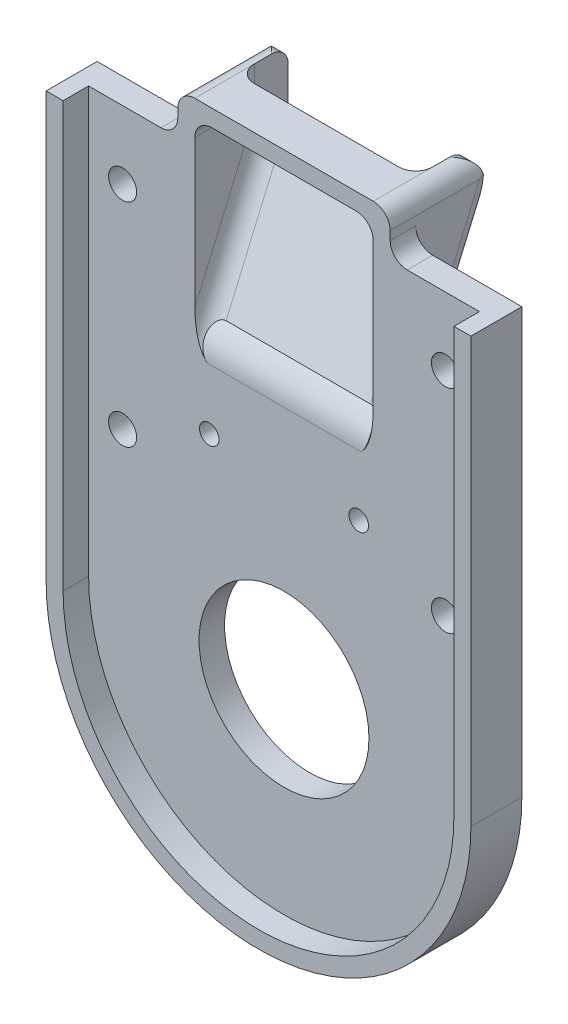
SolidWorks part; units mm, degrees
ref_plane "前视基准面" through (0, 0, 0) normal (0, 0, 1) x (1, 0, 0)
ref_plane "上视基准面" through (0, 0, 0) normal (0, 1, 0) x (1, 0, 0)
ref_plane "右视基准面" through (0, 0, 0) normal (1, 0, 0) x (0, 0, -1)
sketch "草图1" plane through (0, 0, 0) normal (0, 0, 1) x (1, 0, 0)
  line L0 (-25, 0) -> (25, 0)
  line L1 (-25, 0) -> (-25, 50)
  line L2 (25, 0) -> (25, 50)
  line L3 (-25, 50) -> (25, 50)
  line L4 (-23, 0) -> (-23, 50)
  line L5 (23, 0) -> (23, 50)
  circle A0 centre (0, 0) radius 23
  circle A1 centre (0, 0) radius 25
  circle A2 centre (0, 0) radius 10
  circle A3 centre (-19, 17) radius 1.65
  circle A4 centre (19, 17) radius 1.65
  circle A5 centre (19, 42) radius 1.65
  circle A6 centre (-19, 42) radius 1.65
  dimension "D1" = 46
  dimension "D2" = 50
  dimension "D3" = 20
  dimension "D6" = 3.3
  dimension "D4" = 2
  dimension "D5" = 19
  dimension "D7" = 17
  dimension "D10" = 50
  dimension "D8" = 2
  dimension "D9" = 2
extrude "凸台-拉伸3" add sketch "草图1" along normal blind 3 contours A4 A1 L5 L3 L4 A3 A6 A5 | A1 L2 L3 L5 | A1 L4 L3 L1 | A4 A1 A3 L4 A0 L5 | A2 L0 A0 | A2 L0 A0 | L0 A1 A0 | L4 A1 L0 | L0 A1 L5 region at (-23.8028, 3.6947, 0) region at (-24, -0.559, 0) region at (-24.0299, 28.2321, 0) region at (0, 11.0476, 0) region at (-22.4765, 4.899, 0) region at (0, -11.0476, 0) region at (24.0299, 28.2321, 0) region at (23.8028, 3.6947, 0) region at (0, 35.1599, 0)
sketch "草图3" plane through (0, 0, 3) normal (0, 0, 1) x (1, 0, 0)
  line L0 (-23, 0) -> (-23, 50)
  line L1 (23, 0) -> (23, 50)
  line L3 (-25, 50) -> (-25, 0)
  line L4 (25, 0) -> (25, 50)
  line L5 (25, 50) -> (-25, 50)
  line L6 (-25, 50) -> (-25, 0)
  line L7 (25, 0) -> (25, 50)
  line L8 (25, 50) -> (-25, 50)
  circle A0 centre (0, 0) radius 23
  arc A1 (-25, 0) -> (25, 0) centre (0, 0) ccw
  arc A2 (-25, 0) -> (25, 0) centre (0, 0) ccw
  line M6 (-25, 50) -> (-25, 0)
  arc M7 (-25, 0) -> (25, 0) centre (0, 0) ccw
  line M8 (25, 0) -> (25, 50)
  line M9 (25, 50) -> (-25, 50)
  dimension "D2" = 46
  dimension "D1" = 0
extrude "凸台-拉伸4" add sketch "草图3" along normal blind 3 contours A0 L0 L1 M9 M6 M7 M8 region at (0, -23.9014, 3)
sketch "草图4" plane through (0, 0, 3) normal (0, 0, 1) x (1, 0, 0)
  line L0 (0, 50) -> (0, 0) construction
  line L3 (23, 0) -> (23, 50)
  line L4 (23, 50) -> (-23, 50)
  line L5 (-23, 50) -> (-23, 0)
  line L6 (23, 0) -> (23, 50)
  line L7 (23, 50) -> (-23, 50)
  line L8 (-23, 50) -> (-23, 0)
  circle A0 centre (8.8, 21.62) radius 1.15
  arc A1 (-23, 0) -> (23, 0) centre (0, 0) ccw
  arc A2 (-23, 0) -> (23, 0) centre (0, 0) ccw
  circle A3 centre (-8.8, 21.62) radius 1.15
  dimension "D2" = 2.3
  dimension "D3" = 8.8
  dimension "D4" = 28.38
  dimension "D1" = 0
extrude "切除-拉伸1" cut sketch "草图4" against normal blind 10 contours A3 | A0
sketch "草图5" plane through (0, 0, 0) normal (0, 0, -1) x (-1, 0, 0)
  line L1 (-12.5, 50) -> (12.5, 50)
  line L2 (-12.5, 50) -> (-12.5, 30.4832)
  line L3 (25, 0) -> (25, 50)
  line L4 (25, 50) -> (-25, 50)
  line L5 (-25, 50) -> (-25, 0)
  line L6 (25, 0) -> (25, 50)
  line L7 (25, 50) -> (-25, 50)
  line L8 (-25, 50) -> (-25, 0)
  line L9 (-12.5, 30.4832) -> (12.5, 30.4832)
  line L10 (12.5, 50) -> (12.5, 30.4832)
  line L11 (-10.5, 50) -> (-10.5, 32.4832)
  line L12 (-10.5, 32.4832) -> (10.5, 32.4832)
  line L13 (10.5, 32.4832) -> (10.5, 50)
  line L15 (-12.5, 50) -> (-10.5, 50)
  line L16 (-12.5, 50) -> (-12.5, 55)
  line L17 (-12.5, 55) -> (-10.5, 55)
  line L18 (-10.5, 50) -> (-10.5, 55)
  line L19 (10.5, 50) -> (12.5, 50)
  line L20 (10.5, 50) -> (10.5, 55)
  line L21 (10.5, 55) -> (12.5, 55)
  line L22 (12.5, 50) -> (12.5, 55)
  arc A1 (-25, 0) -> (25, 0) centre (0, 0) ccw
  arc A2 (-25, 0) -> (25, 0) centre (0, 0) ccw
  line M11 (25, 50) -> (-25, 50)
  dimension "D2" = 25
  dimension "D3" = 37.5
  dimension "D4" = 2
  dimension "D5" = 2
  dimension "D6" = 2
  dimension "D7" = 5
  dimension "D8" = 5
  dimension "D9" = 19.5168
  dimension "D1" = 0
extrude "凸台-拉伸6" add sketch "草图5" along normal blind 8 contours L13 L12 L11 L7 L2 L9 L10 M11 | L7 L18 L17 L16 | L22 L21 L20 M11 region at (11.5, 52.5, 0) region at (11.5, 49.6828, 0) region at (-11.5, 52.5, 0)
sketch "草图6" plane through (0, 0, 0) normal (0, 0, -1) x (-1, 0, 0)
  line L4 (-10.5, 32.4832) -> (10.5, 32.4832)
  line L5 (10.5, 32.4832) -> (10.5, 50)
  line L7 (10.5, 32.4832) -> (10.5, 50)
  line L8 (-10.5, 32.4832) -> (10.5, 32.4832)
  line L13 (10.5, 50) -> (-10.5, 50)
  line L15 (10.5, 50) -> (-10.5, 50)
  line L16 (-10.5, 50) -> (-10.5, 32.4832)
  line L17 (-10.5, 50) -> (-10.5, 32.4832)
  dimension "D1" = 0
extrude "切除-拉伸2" cut sketch "草图6" against normal blind 10
sketch "草图7" plane through (12.5, 0, 0) normal (1, 0, 0) x (0, 0, -1)
  line L0 (0, 30.4832) -> (8, 49.0245)
  line L1 (8, 55) -> (8, 30.4832) construction
  line L6 (0, 55) -> (0, 50)
  line L8 (0, 55) -> (0, 50)
  line L10 (0, 50) -> (0, 30.4832)
  line L11 (8, 55) -> (0, 55)
  line L16 (8, 55) -> (0, 55)
  line L19 (0, 50) -> (0, 30.4832)
  line L20 (0, 30.4832) -> (8, 30.4832)
  line L21 (0, 30.4832) -> (8, 30.4832)
  line L22 (8, 30.4832) -> (8, 55)
  line L23 (8, 30.4832) -> (8, 55)
  point P3 (10, 49.0245)
  line M8 (0, 30.4832) -> (8, 30.4832)
  line M9 (8, 30.4832) -> (8, 55)
  dimension "D1" = 0
extrude "切除-拉伸3" cut sketch "草图7" against normal blind 50 contours L0 M8 M9 region at (12.5, 36.6636, -5.3333)
sketch "草图8" plane through (0, 4.7843, 11.0883) normal (0, -0.3962, -0.9182) x (-1, 0, 0)
  line L0 (-10.5, 48.1825) -> (10.5, 48.1825)
  line L7 (12.5, 27.989) -> (12.5, 48.1825)
  line L8 (10.5, 30.1673) -> (-10.5, 30.1673)
  line L9 (-10.5, 30.1673) -> (-10.5, 48.1825)
  line L10 (-10.5, 48.1825) -> (-12.5, 48.1825)
  line L11 (-12.5, 48.1825) -> (-12.5, 27.989)
  line L12 (-12.5, 27.989) -> (12.5, 27.989)
  line L16 (10.5, 30.1673) -> (-10.5, 30.1673)
  line L17 (-10.5, 30.1673) -> (-10.5, 48.1825)
  line L18 (-10.5, 48.1825) -> (-12.5, 48.1825)
  line L19 (-12.5, 48.1825) -> (-12.5, 27.989)
  line L20 (-12.5, 27.989) -> (12.5, 27.989)
  line L27 (12.5, 27.989) -> (12.5, 48.1825)
  line L29 (12.5, 48.1825) -> (10.5, 48.1825)
  line L30 (12.5, 48.1825) -> (10.5, 48.1825)
  line L31 (10.5, 48.1825) -> (10.5, 30.1673)
  line L32 (10.5, 48.1825) -> (10.5, 30.1673)
  point P2 (10.0366, 48.1825)
  line M9 (10.5, 30.1673) -> (-10.5, 30.1673)
  line M10 (-10.5, 30.1673) -> (-10.5, 48.1825)
  line M11 (-10.5, 48.1825) -> (-12.5, 48.1825)
  line M12 (-12.5, 48.1825) -> (-12.5, 27.989)
  line M13 (-12.5, 27.989) -> (12.5, 27.989)
  line M14 (12.5, 27.989) -> (12.5, 48.1825)
  line M15 (12.5, 48.1825) -> (10.5, 48.1825)
  line M16 (10.5, 48.1825) -> (10.5, 30.1673)
  dimension "D1" = 0
extrude "凸台-拉伸8" add sketch "草图8" against normal blind 2 contours L0 M10 M9 M16 | M16 M9 M10 M11 M12 M13 M14 M15 region at (0, 40.7538, -4.4315) region at (10.8214, 40.7538, -4.4315)
sketch "草图9" plane through (0, 0, 0) normal (0, 0, 1) x (1, 0, 0)
  line L4 (-12.5, 55) -> (-12.5, 50)
  line L5 (-12.5, 50) -> (-10.5, 50)
  line L6 (-10.5, 50) -> (-10.5, 55)
  line L7 (-10.5, 55) -> (-12.5, 55)
  line L8 (-12.5, 55) -> (-12.5, 50)
  line L9 (-12.5, 50) -> (-10.5, 50)
  line L10 (-10.5, 50) -> (-10.5, 55)
  line L11 (-10.5, 55) -> (-12.5, 55)
  line L12 (10.5, 55) -> (10.5, 50)
  line L13 (10.5, 50) -> (12.5, 50)
  line L14 (12.5, 50) -> (12.5, 55)
  line L15 (12.5, 55) -> (10.5, 55)
  line L16 (10.5, 55) -> (10.5, 50)
  line L17 (10.5, 50) -> (12.5, 50)
  line L18 (12.5, 50) -> (12.5, 55)
  line L19 (12.5, 55) -> (10.5, 55)
  dimension "D1" = 0
  dimension "D2" = 0
extrude "凸台-拉伸9" add sketch "草图9" along normal blind 3
fillet "圆角3" radius 2 4 edges at (10.5, 41.15, -2.4242) (-10.5, 41.15, -2.4242) (-12.5, 50, 1.5) (12.5, 50, 1.5)
sketch "草图10" plane through (0, 55, 0) normal (0, 1, 0) x (1, 0, 0)
  line L1 (-12.5, -3) -> (12.5, -3)
  line L2 (-12.5, -3) -> (-12.5, 2)
  line L3 (-12.5, 2) -> (12.5, 2)
  line L4 (-12.5, 8) -> (-12.5, -3)
  line L5 (-12.5, -3) -> (-10.5, -3)
  line L6 (-10.5, -3) -> (-10.5, 8)
  line L7 (-10.5, 8) -> (-12.5, 8)
  line L8 (-12.5, 8) -> (-12.5, -3)
  line L9 (-12.5, -3) -> (-10.5, -3)
  line L10 (-10.5, -3) -> (-10.5, 8)
  line L11 (-10.5, 8) -> (-12.5, 8)
  line L12 (10.5, 8) -> (10.5, -3)
  line L13 (10.5, -3) -> (12.5, -3)
  line L14 (12.5, -3) -> (12.5, 8)
  line L15 (12.5, 8) -> (10.5, 8)
  line L16 (10.5, 8) -> (10.5, -3)
  line L17 (10.5, -3) -> (12.5, -3)
  line L18 (12.5, -3) -> (12.5, 8)
  line L19 (12.5, 8) -> (10.5, 8)
  line L20 (12.5, -3) -> (12.5, 2)
  line M15 (-10.5, -3) -> (-10.5, 8)
  dimension "D3" = 5
  dimension "D1" = 0
  dimension "D2" = 0
extrude "凸台-拉伸10" add sketch "草图10" against normal blind 2 contours L16 L3 L1 M15 region at (0, 55, 0.5)
sketch "草图11" plane through (0, 44.2402, -19.0883) normal (0, 0.9182, -0.3962) x (1, 0, 0)
  line L4 (-10.5, -12.0764) -> (-10.5, -16.0764)
  line L5 (-8.5, -14.0764) -> (8.5, -14.0764)
  line L6 (10.5, -16.0764) -> (10.5, -12.0764)
  line L7 (10.5, -12.0764) -> (-10.5, -12.0764)
  line L8 (-10.5, -12.0764) -> (-10.5, -16.0764)
  line L9 (-8.5, -14.0764) -> (8.5, -14.0764)
  line L10 (10.5, -16.0764) -> (10.5, -12.0764)
  line L11 (10.5, -12.0764) -> (-10.5, -12.0764)
  arc A2 (-8.5, -14.0764) -> (-10.5, -16.0764) centre (-8.5, -16.0764) ccw
  arc A3 (10.5, -16.0764) -> (8.5, -14.0764) centre (8.5, -16.0764) ccw
  arc A4 (-8.5, -14.0764) -> (-10.5, -16.0764) centre (-8.5, -16.0764) ccw
  arc A5 (10.5, -16.0764) -> (8.5, -14.0764) centre (8.5, -16.0764) ccw
  dimension "D1" = 0
extrude "切除-拉伸4" cut sketch "草图11" against normal blind 2
fillet "圆角4" radius 2 10 edges at (-10.5, 47.9804, -5.3713) (10.5, 47.9804, -5.3713) (11.5, 55, -8) (-11.5, 55, -8) (-10.5, 54, -2) (10.5, 54, -2) (12.5, 55, -2.5) (-12.5, 55, -2.5) (10.5, 53, 0.5) (-10.5, 53, 0.5)
fillet "圆角5" radius 15 1 edges at (0, 30.4832, 0)
fillet "圆角6" radius 2 4 edges at (12.5, 30.4192, -0.31) (-12.5, 30.4192, -0.31) (12.5, 41.1761, -4.6137) (-12.5, 41.1761, -4.6137)
fillet "圆角7" radius 5 1 edges at (0, 32.4832, 3)
